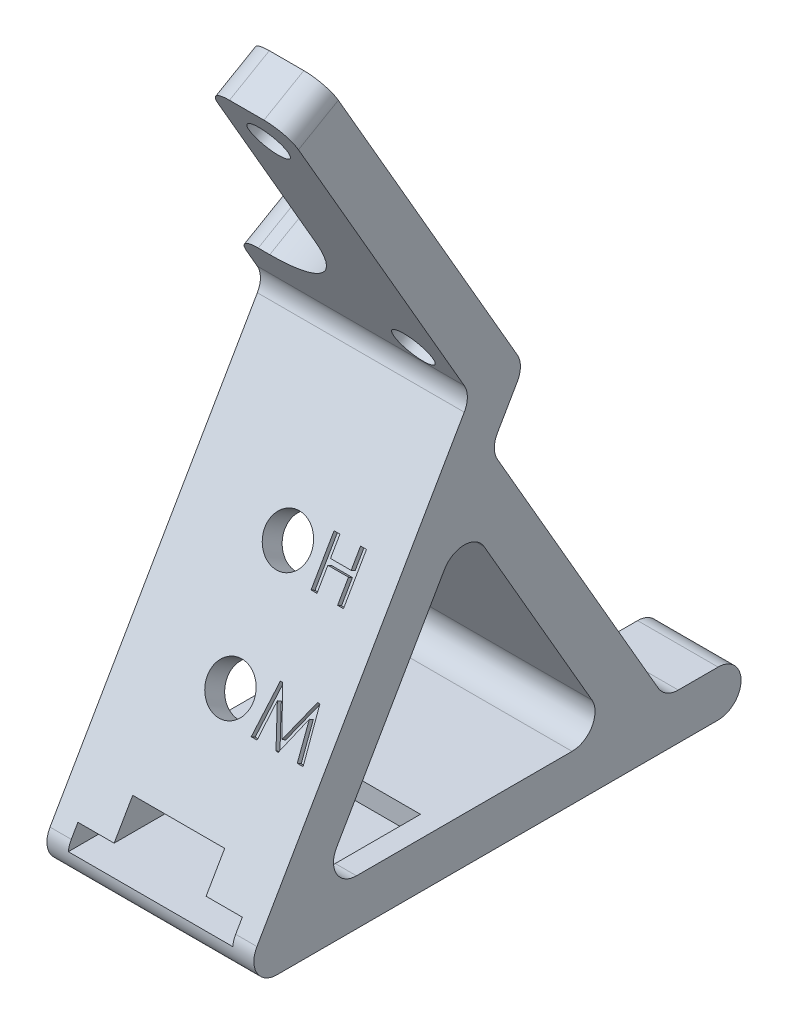
SolidWorks part; units mm, degrees
ref_plane "Plan de face" through (0, 0, 0) normal (0, 0, 1) x (1, 0, 0)
ref_plane "Plan de dessus" through (0, 0, 0) normal (0, 1, 0) x (1, 0, 0)
ref_plane "Plan de droite" through (0, 0, 0) normal (1, 0, 0) x (0, 0, -1)
sketch "Esquisse1" plane through (0, 0, 0) normal (1, 0, 0) x (0, 0, -1)
  line L1 (-37.5, 64.9519) -> (-40.9641, 62.9519)
  line L2 (-40.9641, 62.9519) -> (-24.9641, 35.2391)
  line L3 (-24.9641, 35.2391) -> (-45.3094, 0)
  line L4 (-45.3094, 0) -> (0, 0)
  line L5 (-38.3812, 4) -> (-12.7017, 4)
  line L6 (-12.7017, 4) -> (-25.5415, 26.2391)
  line L7 (-25.5415, 26.2391) -> (-38.3812, 4)
  line L8 (-12.7017, 4) -> (-12.7017, 0) construction
  line L9 (-37.5, 64.9519) -> (-20.3453, 35.2391)
  line L10 (-38.3812, 4) -> (-41.8453, 6) construction
  line L12 (-2.3094, 4) -> (0, 0)
  line L13 (-20.3453, 35.2391) -> (-23.2321, 30.2391)
  line L14 (-23.2321, 30.2391) -> (-8.0829, 4)
  line L15 (-8.0829, 4) -> (-2.3094, 4)
  line L16 (-25.5415, 26.2391) -> (-22.0774, 28.2391) construction
  dimension "D1" = 120
  dimension "D2" = 4
  dimension "D3" = 32
  dimension "D4" = 75
  dimension "D5" = 5
extrude "Boss.-Extru.1" add sketch "Esquisse1" along normal blind 18
hole_wizard "Dégagement M31" positions "Esquisse2" profile "Esquisse3" hole size "M3" standard "ISO" end condition through all
sketch "Esquisse2" plane through (0, 0, 0) normal (0, 0.5, -0.866) x (-1, 0, 0)
  line L3 (-14.5, 46) -> (-14.5, 71.2) construction
  line L7 (-18, 75) -> (0, 75) construction
  line L8 (-18, 40.6906) -> (-18, 75) construction
  point P0 (-14.5, 71.2)
  point P2 (-14.5, 46)
  dimension "D1" = 25.2
  dimension "D2" = 3.8
  dimension "D3" = 3.5
sketch "Esquisse3" plane through (14.5, 61.661, 35.6) normal (1, 0, 0) x (0, 0.866, 0.5)
  line L0 (0, 0) -> (0, 39.2391)
  line L1 (0, 39.2391) -> (1.7, 39.2391)
  line L2 (1.7, 39.2391) -> (1.7, 0)
  line L5 (1.7, 0) -> (0, 0)
  line L11 (0, -6.35) -> (0, 107.95) construction
  dimension "Diamètre du perçage jusqu'au prochain" = 3.4
  dimension "Profondeur du perçage jusqu'au prochain" = 39.2391
sketch "Esquisse7" plane through (0, -2, 3.4641) normal (0, -0.5, 0.866) x (1, 0, 0)
  line L0 (0, 75) -> (11, 75)
  line L1 (18, 75) -> (0, 75) construction
  line L2 (11, 75) -> (11, 48)
  line L3 (11, 48) -> (0, 48)
  line L4 (0, 75) -> (0, 43) construction
  line L5 (0, 48) -> (0, 75)
  line L6 (18, 75) -> (18, 43) construction
  line L7 (18, 43) -> (0, 43) construction
  dimension "D1" = 7
  dimension "D2" = 5
extrude "Enlèv. mat.-Extru.5" cut sketch "Esquisse7" against normal up to next
sketch "Esquisse8" plane through (0, 0, 0) normal (-1, 0, 0) x (0, 0, 1)
  line L0 (0, 0) -> (2.3094, 4)
  line L1 (2.3094, 4) -> (8.0829, 4)
  line L5 (45.3094, 0) -> (0, 0) construction
  line L6 (5.7735, 0) -> (0, 0)
  line L13 (8.0829, 4) -> (5.7735, 0)
extrude "Enlèv. mat.-Extru.6" cut sketch "Esquisse8" against normal offset from surface (11 mm away) 7 up to face at (18, 26.2912, 22.523)
sketch "Esquisse4" plane through (0, 4, 0) normal (0, 1, 0) x (1, 0, 0)
  line L0 (9, -38.3812) -> (9, -36.4047) construction
  line L1 (1.85, -45.3094) -> (16.15, -45.3094)
  line L2 (1.85, -45.3094) -> (1.85, -27.5)
  line L3 (1.85, -27.5) -> (16.15, -27.5)
  line L4 (16.15, -45.3094) -> (16.15, -27.5)
  line L5 (1.85, -45.3094) -> (16.15, -27.5) construction
  line L6 (1.85, -27.5) -> (16.15, -45.3094) construction
  line L7 (18, -38.3812) -> (0, -38.3812) construction
  line L15 (18, -45.3094) -> (0, -45.3094) construction
  point P0 (9, -36.4047)
  point P12 (18, -43)
  dimension "D1" = 14.3
  dimension "D2" = 15.5
extrude "Enlèv. mat.-Extru.1" cut sketch "Esquisse4" against normal blind 1.8
ref_plane "Plan1" through (0, 0, 45.3094) normal (0, 0, -1) x (-1, 0, 0)
sketch "Esquisse5" plane through (0, 0, 45.3094) normal (0, 0, -1) x (-1, 0, 0)
  line L1 (-5, 6.8) -> (-13, 6.8)
  line L2 (-5, 6.8) -> (-5, 4)
  line L3 (-5, 4) -> (-13, 4)
  line L4 (-13, 6.8) -> (-13, 4)
  line L5 (-5, 6.8) -> (-13, 4) construction
  line L6 (-5, 4) -> (-13, 6.8) construction
  line L7 (-16.15, 4) -> (-1.85, 4) construction
  point P0 (-9, 5.4)
  point P6 (-9, 4)
  dimension "D1" = 8
  dimension "D2" = 2.8
extrude "Enlèv. mat.-Extru.2" cut sketch "Esquisse5" along normal up to next
sketch "Esquisse6" plane through (0, 19.6195, 33.9821) normal (0, 0.5, 0.866) x (1, 0, 0)
  line L0 (9, -5.8027) -> (9, -14.8027) construction
  line L1 (5.4, -2.5777) -> (12.6, -2.5777)
  line L2 (5.4, -2.5777) -> (5.4, -9.0277)
  line L3 (5.4, -9.0277) -> (12.6, -9.0277)
  line L4 (12.6, -2.5777) -> (12.6, -9.0277)
  line L5 (5.4, -2.5777) -> (12.6, -9.0277) construction
  line L6 (5.4, -9.0277) -> (12.6, -2.5777) construction
  line L7 (5, -14.8027) -> (13, -14.8027) construction
  line L8 (5.4, 7.4223) -> (12.6, 7.4223)
  line L9 (12.6, 7.4223) -> (12.6, 0.9723)
  line L10 (5.4, 0.9723) -> (12.6, 0.9723)
  line L11 (5.4, 7.4223) -> (5.4, 0.9723)
  circle A0 centre (9, -5.8027) radius 2
  circle A1 centre (9, 4.1973) radius 2
  point P0 (9, -5.8027)
  dimension "D3" = 4
  dimension "D1" = 7.2
  dimension "D2" = 6.45
  dimension "D5" = 9
  dimension "D4" = 2
extrude "Enlèv. mat.-Extru.3" cut sketch "Esquisse6" against normal up to next from offset 2 contours L8 L9 L10 L11 | L1 L4 L3 L2 offset against normal yes
extrude "Enlèv. mat.-Extru.4" cut sketch "Esquisse6<3>" against normal up to next contours A1 | A0
sketch "Esquisse6<3>" plane through (0, 19.6195, 33.9821) normal (0, 0.5, 0.866) x (1, 0, 0) same geometry as "Esquisse6"
sketch "Esquisse9" plane through (0, 19.6195, 33.9821) normal (0, 0.5, 0.866) x (1, 0, 0)
  line L0 (11.5, 2.1973) -> (18, 2.1973) construction
  line L3 (18, 18.0359) -> (18, -22.6547) construction
  line L4 (11.5, -7.8027) -> (18, -7.8027) construction
  circle A0 centre (9, 4.1973) radius 2 construction
  circle A1 centre (9, -5.8027) radius 2 construction
  text T0 "H" font "Century Gothic" height 4
  text T1 "M" font "Century Gothic" height 4
  dimension "D1" = 2
  dimension "D2" = 2
  dimension "D3" = 2.5
extrude "Enlèv. mat.-Extru.7" cut sketch "Esquisse9" against normal blind 0.4
fillet "Congé1" radius 2 15 edges at (0.925, 4, 38.3812) (17.075, 4, 38.3812) (9, 4, 12.7017) (9, 26.2391, 25.5415) (9, 35.2391, 24.9641) (9, 0, 45.3094) (18, 63.9519, 39.2321) (9, 35.2391, 20.3453) (9, 30.2391, 23.2321) (14.5, 4, 8.0829) (14.5, 4, 2.3094) (14.5, 0, 0) (0, 40.5692, 25.7321) (11, 63.9519, 39.2321) (5.5, 0, 5.7735)
fillet "Congé2" radius 8 1 edges at (11, 40.5692, 25.7321)
